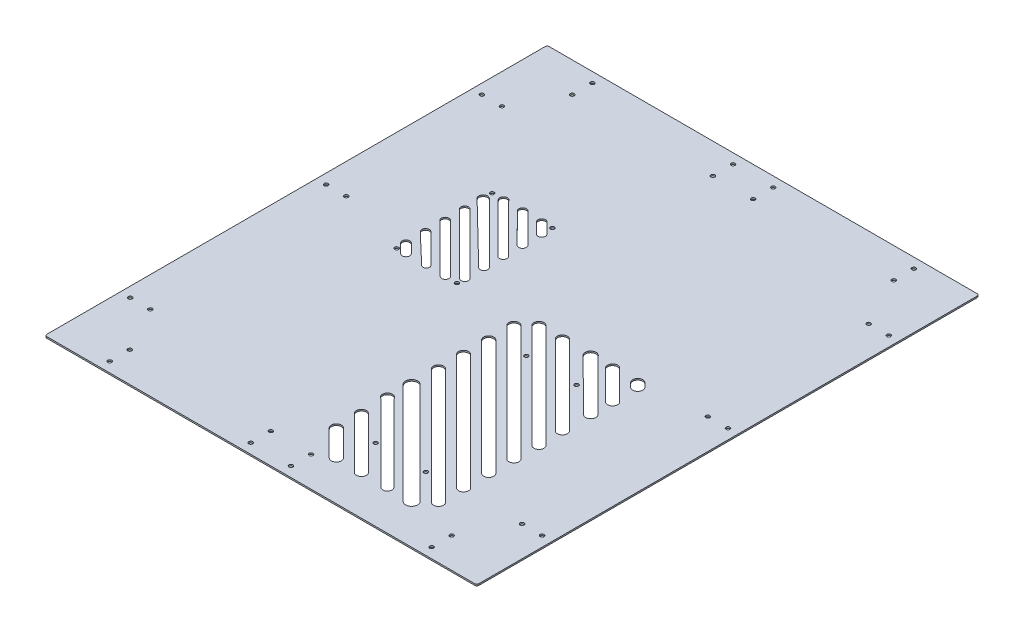
SolidWorks part; units mm, degrees
ref_plane "Front Plane" through (0, 0, 0) normal (0, 0, 1) x (1, 0, 0)
ref_plane "Top Plane" through (0, 0, 0) normal (0, 1, 0) x (1, 0, 0)
ref_plane "Right Plane" through (0, 0, 0) normal (1, 0, 0) x (0, 0, -1)
sketch "Sketch1" plane through (0, 0, 0) normal (0, 1, 0) x (1, 0, 0)
  line L1 (-215, -250) -> (215, -250)
  line L2 (-215, -250) -> (-215, 250)
  line L3 (-215, 250) -> (215, 250)
  line L4 (215, -250) -> (215, 250)
  line L5 (-215, -250) -> (215, 250) construction
  line L6 (-215, 250) -> (215, -250) construction
  point P0 (0, 0)
  dimension "D1" = 430
  dimension "D2" = 500
extrude "Boss-Extrude1" add sketch "Sketch1" along normal blind 1.5
sketch "Sketch6" plane through (0, 1.5, 0) normal (0, 1, 0) x (1, 0, 0)
  circle A0 centre (92.2927, -28) radius 1.95
  circle A1 centre (42.2927, -28) radius 1.95
  circle A2 centre (92.2927, -178) radius 1.95
  circle A3 centre (42.2927, -178) radius 1.95
  dimension "D1" = 50
  dimension "D2" = 150
sketch "Sketch7" plane through (0, 1.5, 0) normal (0, 1, 0) x (1, 0, 0)
  circle A0 centre (-114.98, 95.1924) radius 1.95
  circle A1 centre (-54.98, 95.1924) radius 1.95
  circle A2 centre (-54.98, 0.1924) radius 1.95
  circle A3 centre (-114.98, 0.1924) radius 1.95
  dimension "D1" = 95
  dimension "D2" = 60
sketch "Sketch12" plane through (0, 0, 0) normal (0, -1, 0) x (-1, 0, 0)
  line L0 (215, -250) -> (-215, -250) construction
  line L1 (-215, 250) -> (215, 250) construction
  line L2 (215, 250) -> (215, -250) construction
  line L3 (-215, -250) -> (-215, 250) construction
  circle A0 centre (-185, -175) radius 1.95
  circle A1 centre (-205, 170) radius 1.95
  circle A3 centre (-185, 10) radius 1.95
  circle A4 centre (-205, 10) radius 1.95
  circle A5 centre (-205, -175) radius 1.95
  circle A6 centre (-185, 170) radius 1.95
  circle A7 centre (205, -175) radius 1.95
  circle A8 centre (205, 20) radius 1.95
  circle A9 centre (185, 175) radius 1.95
  circle A10 centre (205, 175) radius 1.95
  circle A11 centre (185, -175) radius 1.95
  circle A12 centre (185, 20) radius 1.95
  circle A13 centre (160.3499, -240) radius 1.95
  circle A14 centre (160.3499, -220) radius 1.95
  circle A15 centre (20, -240) radius 1.95
  circle A16 centre (20, -220) radius 1.95
  circle A17 centre (-20, -220) radius 1.95
  circle A19 centre (-20, -240) radius 1.95
  circle A20 centre (-160, -240) radius 1.95
  circle A21 centre (-160, -220) radius 1.95
  circle A22 centre (160, 220) radius 1.95
  circle A23 centre (160, 240) radius 1.95
  circle A24 centre (20, 220) radius 1.95
  circle A25 centre (20, 240) radius 1.95
  circle A26 centre (-20, 220) radius 1.95
  circle A27 centre (-20, 240) radius 1.95
  circle A28 centre (-160, 220) radius 1.95
  circle A29 centre (-160, 240) radius 1.95
  dimension "D1" = 10
  dimension "D2" = 20
  dimension "D3" = 10
  dimension "D5" = 10
  dimension "D6" = 20
  dimension "D7" = 20
  dimension "D4" = 20
  dimension "D8" = 10
extrude "Cut-Extrude3" cut sketch "Sketch12" against normal blind 50.8
extrude "Cut-Extrude4" cut sketch "Sketch6" against normal blind 50.8
extrude "Cut-Extrude5" cut sketch "Sketch7" against normal blind 50.8
fillet "Fillet1" radius 2 4 edges at (215, 0.75, -250) (215, 0.75, 250) (-215, 0.75, 250) (-215, 0.75, -250)
sketch "Sketch13" plane through (0, 0, 0) normal (0, -1, 0) x (1, 0, 0)
  line L0 (67.2927, 28) -> (67.2927, 178) construction
  line L6 (92.2927, 178) -> (42.2927, 178) construction
  line L8 (92.2927, 178) -> (92.2927, 28) construction
  line L9 (92.2927, 28) -> (42.2927, 28) construction
  line L10 (42.2927, 178) -> (42.2927, 28) construction
  line L11 (67.2927, 103) -> (42.2927, 103) construction
  line L12 (124.7927, 122.9451) -> (9.7927, 7.9451) construction
  line L13 (124.7927, 210.5) -> (9.7927, 210.5)
  line L14 (124.7927, 210.5) -> (124.7927, -4.5)
  line L15 (124.7927, -4.5) -> (9.7927, -4.5)
  line L16 (9.7927, 210.5) -> (9.7927, -4.5)
  line L17 (124.7927, 210.5) -> (9.7927, -4.5) construction
  line L18 (124.7927, -4.5) -> (9.7927, 210.5) construction
  line L19 (128.3282, 119.4095) -> (13.3282, 4.4095)
  line L20 (121.2572, 126.4806) -> (6.2572, 11.4806)
  line L21 (124.7927, 147.9451) -> (9.7927, 32.9451) construction
  line L22 (128.3282, 144.4095) -> (13.3282, 29.4095)
  line L23 (121.2572, 151.4806) -> (6.2572, 36.4806)
  line L26 (124.7927, 172.9451) -> (9.7927, 57.9451) construction
  line L29 (128.3282, 169.4095) -> (13.3282, 54.4095)
  line L32 (121.2572, 176.4806) -> (6.2572, 61.4806)
  line L35 (124.7927, 197.9451) -> (9.7927, 82.9451) construction
  line L38 (128.3282, 194.4095) -> (13.3282, 79.4095)
  line L41 (121.2572, 201.4806) -> (6.2572, 86.4806)
  line L44 (110.6506, 210.5) -> (9.7927, 109.6421) construction
  line L47 (114.8916, 206.259) -> (14.0337, 105.4011)
  line L50 (102.1686, 210.5) -> (5.5517, 113.8831)
  line L53 (-54.98, -95.1924) -> (-114.98, -95.1924) construction
  line L58 (-114.98, -95.1924) -> (-114.98, -44.2867) construction
  line L62 (86.5307, 210.5) -> (8.6916, 132.661) construction
  line L65 (-114.98, -0.1924) -> (-54.98, -0.1924) construction
  line L66 (-54.98, -0.1924) -> (-54.98, -95.1924) construction
  line L67 (-54.98, -84.5868) -> (-65.5855, -95.1924) construction
  line L68 (-54.98, -89.8901) -> (-60.2822, -95.1924)
  line L69 (-57.6303, -81.9365) -> (-68.2358, -92.5421)
  line L70 (-54.98, -95.1924) -> (-114.98, -0.1924) construction
  line L71 (-54.98, -65.4331) -> (-84.7393, -95.1924) construction
  line L72 (-54.98, -70.7364) -> (-79.4324, -95.1924)
  line L73 (-57.6384, -62.7886) -> (-87.2428, -92.5491)
  line L74 (-54.98, -46.2793) -> (-103.893, -95.1924) construction
  line L75 (-54.98, -51.5826) -> (-98.5897, -95.1924)
  line L76 (-57.6398, -43.6363) -> (-106.2442, -92.5505)
  line L77 (-54.98, -27.1256) -> (-120.2706, -91.5396) construction
  line L78 (-54.98, -32.4289) -> (-111.9255, -89.3745)
  line L79 (-57.5955, -24.4383) -> (-117.9928, -83.2246)
  line L80 (-52.4189, -5.4139) -> (-114.98, -67.9718) construction
  line L81 (-52.3742, -10.6694) -> (-112.3283, -70.6235)
  line L83 (-63.9533, 2.3637) -> (-114.98, -48.8181) construction
  line L84 (-63.9494, -2.7446) -> (-112.3283, -51.1235)
  line L87 (-71.6576, -0.1924) -> (-114.98, -43.5148)
  line L88 (-85.508, -0.1924) -> (-114.98, -29.6644) construction
  line L91 (-83.2026, -2.4978) -> (-112.3283, -31.6235)
  line L92 (-90.2324, -0.1924) -> (-114.98, -23.7903)
  line L93 (-105.7005, -0.1924) -> (-114.98, -10.5106) construction
  line L96 (-103.0489, -2.844) -> (-112.3283, -12.1235)
  line L99 (-111.0038, -0.1924) -> (-114.98, -4.1685)
  line L102 (-60.2822, -95.1924) -> (-62.9366, -97.844)
  line L105 (-98.5897, -95.1924) -> (-100.7736, -97.6705)
  line L106 (-79.4324, -95.1924) -> (-81.8594, -97.7646)
  line L107 (-114.98, -62.6685) -> (-117.6316, -65.3202)
  line L108 (-114.98, -43.5148) -> (-117.4324, -45.635)
  line L109 (-114.98, -4.1685) -> (-117.6316, -6.8202)
  line L110 (-54.98, -89.8901) -> (-52.3283, -87.2358)
  line L111 (-54.98, -70.7364) -> (-52.3283, -68.0843)
  line L112 (-54.98, -51.5826) -> (-52.3283, -48.9306)
  line L113 (-54.98, -32.4289) -> (-52.3283, -29.7772)
  line L114 (-57.5857, -5.4578) -> (-114.98, -62.6685)
  line L115 (-90.2324, -0.1924) -> (-87.7579, 2.1672)
  line L116 (-71.6576, -0.1924) -> (-69.0283, 2.3851)
  line L117 (-111.0038, -0.1924) -> (-108.3522, 2.4593)
  line L118 (-114.98, -23.7903) -> (-117.5678, -26.2579)
  line L119 (89.7127, 207.318) -> (13.4147, 131.0201)
  line L120 (80.1667, 210.5) -> (7.0508, 137.3841)
  line L121 (60.6506, 210.5) -> (9.7927, 159.6421) construction
  line L122 (64.1861, 206.9645) -> (13.3282, 156.1066)
  line L123 (53.5795, 210.5) -> (6.2572, 163.1777)
  line L124 (35.6506, 210.5) -> (9.7927, 184.6421) construction
  line L125 (39.1861, 206.9645) -> (13.3282, 181.1066)
  line L126 (28.5795, 210.5) -> (6.2572, 188.1777)
  line L127 (10.6506, 210.5) -> (9.7927, 209.6421) construction
  line L128 (16.6674, 209.4458) -> (13.3282, 206.1066)
  line L130 (128.3284, -3.8936) -> (124.1859, -8.0357)
  line L133 (125.6429, 98.792) -> (22.3509, -4.5) construction
  line L134 (129.1784, 95.2564) -> (29.422, -4.5)
  line L135 (122.1073, 102.3275) -> (18.8154, -0.9645)
  line L136 (124.7927, 74.6421) -> (45.6506, -4.5) construction
  line L137 (128.3282, 71.1066) -> (52.7216, -4.5)
  line L138 (121.2572, 78.1777) -> (42.115, -0.9645)
  line L139 (124.7927, 46.436) -> (73.8567, -4.5) construction
  line L140 (128.4341, 42.7783) -> (80.9436, -4.5)
  line L141 (121.1513, 50.0937) -> (70.1015, -0.728)
  line L142 (124.7927, 24.6421) -> (95.6506, -4.5) construction
  line L143 (128.3282, 21.1066) -> (102.7216, -4.5)
  line L144 (121.2572, 28.1777) -> (92.115, -0.9645)
  line L145 (124.7928, -0.358) -> (120.6506, -4.5) construction
  line L147 (121.2572, 3.1777) -> (117.115, -0.9645)
  line L166 (6.6802, 213.5553) -> (10.376, 216.4949)
  line L167 (28.5795, 210.5) -> (32.115, 214.0355)
  line L168 (53.5795, 210.5) -> (57.115, 214.0355)
  line L169 (80.1667, 210.5) -> (83.3487, 213.682)
  line L170 (102.1686, 210.5) -> (106.4096, 214.741)
  line L171 (102.7216, -4.5) -> (99.1861, -8.0355)
  line L172 (80.9436, -4.5) -> (77.854, -8.0143)
  line L173 (52.7216, -4.5) -> (49.1861, -8.0355)
  line L174 (29.422, -4.5) -> (25.8864, -8.0355)
  line L356 (124.7927, 347.9451) -> (9.7927, 232.9451) construction
  line L357 (128.3282, 344.4095) -> (13.3282, 229.4095) [skipped]
  line L358 (121.2572, 351.4806) -> (6.2572, 236.4806) [skipped]
  line L359 (124.7927, 322.9451) -> (9.7927, 207.9451) construction
  line L360 (128.3282, 319.4095) -> (13.3282, 204.4095) [skipped]
  line L361 (121.2572, 326.4806) -> (6.2572, 211.4806) [skipped]
  line L362 (124.7927, 297.9451) -> (9.7927, 182.9451) construction
  line L363 (128.3282, 294.4095) -> (13.3282, 179.4095) [skipped]
  line L364 (121.2572, 301.4806) -> (6.2572, 186.4806) [skipped]
  line L365 (124.7927, 272.9451) -> (9.7927, 157.9451) construction
  line L366 (128.3282, 269.4095) -> (13.3282, 154.4095) [skipped]
  line L367 (121.2572, 276.4806) -> (6.2572, 161.4806) [skipped]
  line L368 (124.7927, 247.9451) -> (9.7927, 132.9451) construction
  line L369 (128.3282, 244.4095) -> (13.3282, 129.4095) [skipped]
  line L370 (121.2572, 251.4806) -> (6.2572, 136.4806) [skipped]
  line L371 (124.7927, 222.9451) -> (9.7927, 107.9451) construction
  line L372 (128.3282, 219.4095) -> (13.3282, 104.4095) [skipped]
  line L373 (121.2572, 226.4806) -> (6.2572, 111.4806) [skipped]
  line L374 (124.7927, 347.9451) -> (9.7927, 232.9451) construction
  line L375 (128.3282, 344.4095) -> (13.3282, 229.4095) [skipped]
  line L376 (121.2572, 351.4806) -> (6.2572, 236.4806) [skipped]
  line L377 (124.7927, 322.9451) -> (9.7927, 207.9451) construction
  line L378 (128.3282, 319.4095) -> (13.3282, 204.4095) [skipped]
  line L379 (121.2572, 326.4806) -> (6.2572, 211.4806) [skipped]
  line L380 (124.7927, 297.9451) -> (9.7927, 182.9451) construction
  line L381 (128.3282, 294.4095) -> (13.3282, 179.4095) [skipped]
  line L382 (121.2572, 301.4806) -> (6.2572, 186.4806) [skipped]
  line L383 (124.7927, 272.9451) -> (9.7927, 157.9451) construction
  line L384 (128.3282, 269.4095) -> (13.3282, 154.4095) [skipped]
  line L385 (121.2572, 276.4806) -> (6.2572, 161.4806) [skipped]
  line L386 (124.7927, 247.9451) -> (9.7927, 132.9451) construction
  line L387 (128.3282, 244.4095) -> (13.3282, 129.4095) [skipped]
  line L388 (121.2572, 251.4806) -> (6.2572, 136.4806) [skipped]
  line L389 (124.7927, 222.9451) -> (9.7927, 107.9451) construction
  line L390 (128.3282, 219.4095) -> (13.3282, 104.4095) [skipped]
  line L391 (121.2572, 226.4806) -> (6.2572, 111.4806) [skipped]
  arc A32 (128.3282, 119.4095) -> (121.2572, 126.4806) centre (124.7927, 122.9451) ccw
  arc A59 (-68.2358, -92.5421) -> (-62.9366, -97.844) centre (-65.5855, -95.1924) ccw
  arc A60 (-87.2428, -92.5491) -> (-81.8594, -97.7646) centre (-84.5855, -95.1924) ccw
  arc A61 (-106.2442, -92.5505) -> (-100.7736, -97.6705) centre (-103.5855, -95.1924) ccw
  arc A63 (-117.6316, -65.3202) -> (-112.3283, -70.6235) centre (-114.98, -67.9718) ccw
  arc A64 (-117.4324, -45.635) -> (-112.3283, -51.1235) centre (-114.98, -48.4718) ccw
  arc A65 (-117.5678, -26.2579) -> (-112.3283, -31.6235) centre (-114.98, -28.9718) ccw
  arc A66 (-117.6316, -6.8202) -> (-112.3283, -12.1235) centre (-114.98, -9.4718) ccw
  arc A67 (-52.3283, -29.7772) -> (-57.5955, -24.4383) centre (-54.98, -27.1256) ccw
  arc A68 (-52.3283, -48.9306) -> (-57.6398, -43.6363) centre (-54.98, -46.2793) ccw
  arc A69 (-52.3283, -68.0843) -> (-57.6384, -62.7886) centre (-54.98, -65.4331) ccw
  arc A70 (-52.3283, -87.2358) -> (-57.6303, -81.9365) centre (-54.98, -84.5868) ccw
  arc A71 (-52.3742, -10.6694) -> (-57.5857, -5.4578) centre (-54.98, -8.0636) ccw
  arc A72 (-117.9928, -83.2246) -> (-111.9255, -89.3745) centre (-114.98, -86.32) ccw
  arc A73 (6.2572, 11.4806) -> (13.3282, 4.4095) centre (9.7927, 7.9451) ccw
  arc A74 (128.3282, 144.4095) -> (121.2572, 151.4806) centre (124.7927, 147.9451) ccw
  arc A75 (6.2572, 36.4806) -> (13.3282, 29.4095) centre (9.7927, 32.9451) ccw
  arc A76 (128.3282, 169.4095) -> (121.2572, 176.4806) centre (124.7927, 172.9451) ccw
  arc A77 (6.2572, 61.4806) -> (13.3282, 54.4095) centre (9.7927, 57.9451) ccw
  circle A78 centre (-122.5855, -95.1924) radius 3.7481 [skipped]
  arc A79 (-83.2026, -2.4978) -> (-87.7579, 2.1672) centre (-85.508, -0.1924) ccw
  arc A80 (-103.0489, -2.844) -> (-108.3522, 2.4593) centre (-105.7005, -0.1924) ccw
  arc A81 (-63.9494, -2.7446) -> (-69.0283, 2.3851) centre (-66.5016, -0.1924) ccw
  arc A82 (128.3282, 194.4095) -> (121.2572, 201.4806) centre (124.7927, 197.9451) ccw
  arc A83 (6.2572, 86.4806) -> (13.3282, 79.4095) centre (9.7927, 82.9451) ccw
  arc A85 (5.5517, 113.8831) -> (14.0337, 105.4011) centre (9.7927, 109.6421) ccw
  arc A87 (7.0508, 137.3841) -> (13.4147, 131.0201) centre (8.6916, 132.661) ccw
  arc A89 (6.2572, 163.1777) -> (13.3282, 156.1066) centre (9.7927, 159.6421) ccw
  arc A91 (6.2572, 188.1777) -> (13.3282, 181.1066) centre (9.7927, 184.6421) ccw
  arc A93 (6.6802, 213.5553) -> (13.3282, 206.1066) centre (9.7927, 209.6421) ccw
  arc A96 (129.1784, 95.2564) -> (122.1073, 102.3275) centre (125.6429, 98.792) ccw
  arc A98 (128.3282, 71.1066) -> (121.2572, 78.1777) centre (124.7927, 74.6421) ccw
  arc A100 (128.4341, 42.7783) -> (121.1513, 50.0937) centre (124.7927, 46.436) ccw
  arc A102 (128.3282, 21.1066) -> (121.2572, 28.1777) centre (124.7927, 24.6421) ccw
  arc A104 (128.3284, -3.8936) -> (121.2572, 3.1777) centre (124.7928, -0.358) ccw
  arc A118 (117.115, -0.9645) -> (124.1859, -8.0357) centre (120.6506, -4.5) ccw
  arc A119 (92.115, -0.9645) -> (99.1861, -8.0355) centre (95.6506, -4.5) ccw
  arc A120 (70.1015, -0.728) -> (77.854, -8.0143) centre (73.8567, -4.5) ccw
  arc A121 (42.115, -0.9645) -> (49.1861, -8.0355) centre (45.6506, -4.5) ccw
  arc A122 (18.8154, -0.9645) -> (25.8864, -8.0355) centre (22.3509, -4.5) ccw
  arc A123 (114.8916, 206.259) -> (106.4096, 214.741) centre (110.6506, 210.5) ccw
  arc A124 (89.7127, 207.318) -> (83.3487, 213.682) centre (86.5307, 210.5) ccw
  arc A125 (64.1861, 206.9645) -> (57.115, 214.0355) centre (60.6506, 210.5) ccw
  arc A126 (39.1861, 206.9645) -> (32.115, 214.0355) centre (35.6506, 210.5) ccw
  arc A127 (16.6674, 209.4458) -> (10.376, 216.4949) centre (13.3216, 212.7917) ccw
  arc A261 (128.3282, 344.4095) -> (121.2572, 351.4806) centre (124.7927, 347.9451) ccw [skipped]
  arc A262 (6.2572, 236.4806) -> (13.3282, 229.4095) centre (9.7927, 232.9451) ccw [skipped]
  arc A263 (128.3282, 319.4095) -> (121.2572, 326.4806) centre (124.7927, 322.9451) ccw [skipped]
  arc A264 (6.2572, 211.4806) -> (13.3282, 204.4095) centre (9.7927, 207.9451) ccw [skipped]
  arc A265 (128.3282, 294.4095) -> (121.2572, 301.4806) centre (124.7927, 297.9451) ccw [skipped]
  arc A266 (6.2572, 186.4806) -> (13.3282, 179.4095) centre (9.7927, 182.9451) ccw [skipped]
  arc A267 (128.3282, 269.4095) -> (121.2572, 276.4806) centre (124.7927, 272.9451) ccw [skipped]
  arc A268 (6.2572, 161.4806) -> (13.3282, 154.4095) centre (9.7927, 157.9451) ccw [skipped]
  arc A269 (128.3282, 244.4095) -> (121.2572, 251.4806) centre (124.7927, 247.9451) ccw [skipped]
  arc A270 (6.2572, 136.4806) -> (13.3282, 129.4095) centre (9.7927, 132.9451) ccw [skipped]
  arc A271 (128.3282, 219.4095) -> (121.2572, 226.4806) centre (124.7927, 222.9451) ccw [skipped]
  arc A272 (6.2572, 111.4806) -> (13.3282, 104.4095) centre (9.7927, 107.9451) ccw [skipped]
  point P18 (67.2927, 65.4451)
  point P23 (67.2927, 90.4451)
  point P30 (67.2927, 115.4451)
  point P37 (67.2927, 140.4451)
  point P46 (67.2927, 167.1421)
  point P54 (67.2927, 192.1421)
  point P73 (67.2927, 217.1421)
  point P85 (67.2927, 153)
  point P89 (-59.0853, -88.6922)
  point P94 (67.2927, 42.1421)
  point P102 (67.2927, 17.1421)
  point P116 (67.2927, 193)
  point P124 (-66.4512, -76.9043)
  point P125 (67.2927, 173)
  point P135 (-73.8171, -65.1165)
  point P151 (-81.183, -53.3286)
  point P153 (67.2927, 193)
  point P156 (67.2927, 292.1421)
  point P159 (-88.5489, -41.5407)
  point P160 (67.2927, 173)
  point P167 (67.2927, 153)
  point P168 (-95.9147, -29.7529)
  point P174 (67.2927, 193)
  point P176 (-103.2806, -17.965)
  point P181 (67.2927, 173)
  point P184 (-110.6465, -6.1771)
  point P188 (67.2927, 153)
  point P207 (67.2927, 267.1421)
  point P227 (67.2927, 242.1421)
  point P235 (67.2927, 192.1421)
  point P242 (67.2927, 167.1421)
  point P251 (67.2927, 193)
  point P258 (67.2927, 173)
  point P265 (67.2927, 153)
  point P272 (67.2927, 193)
  point P279 (67.2927, 173)
  point P286 (67.2927, 153)
  point P321 (67.2927, 193)
  point P328 (67.2927, 173)
  point P335 (67.2927, 153)
  point P342 (67.2927, 193)
  point P349 (67.2927, 173)
  point P356 (67.2927, 153)
  point P365 (67.2927, 193)
  point P372 (67.2927, 173)
  point P379 (67.2927, 153)
  point P386 (67.2927, 193)
  point P393 (67.2927, 173)
  point P400 (67.2927, 153)
  point P407 (67.2927, 193)
  point P414 (67.2927, 173)
  point P421 (67.2927, 153)
  point P428 (67.2927, 193)
  point P435 (67.2927, 173)
  point P442 (67.2927, 153)
  point P449 (67.2927, 193)
  point P456 (67.2927, 173)
  point P463 (67.2927, 153)
  point P470 (67.2927, 193)
  point P477 (67.2927, 173)
  point P484 (67.2927, 153)
  point P491 (67.2927, 193)
  point P498 (67.2927, 173)
  point P505 (67.2927, 153)
  point P512 (67.2927, 193)
  point P519 (67.2927, 173)
  point P526 (67.2927, 153)
  point P533 (67.2927, 193)
  point P540 (67.2927, 173)
  point P547 (67.2927, 153)
  point P554 (67.2927, 193)
  point P561 (67.2927, 173)
  point P568 (67.2927, 153)
  point P575 (67.2927, 193)
  point P582 (67.2927, 173)
  point P589 (67.2927, 153)
  point P596 (67.2927, 193)
  point P603 (67.2927, 173)
  point P610 (67.2927, 153)
  point P617 (67.2927, 193)
  point P624 (67.2927, 173)
  point P631 (67.2927, 153)
  point P638 (67.2927, 193)
  point P645 (67.2927, 173)
  point P652 (67.2927, 153)
  point P677 (67.2927, 292.1421)
  point P684 (67.2927, 267.1421)
  point P691 (67.2927, 242.1421)
  point P698 (67.2927, 217.1421)
  point P705 (67.2927, 192.1421)
  point P712 (67.2927, 167.1421)
  point P719 (67.2927, 288.6066)
  point P726 (67.2927, 263.6066)
  point P733 (67.2927, 238.6066)
  point P740 (67.2927, 213.6066)
  point P747 (67.2927, 188.6066)
  point P754 (67.2927, 163.6066)
  point P761 (67.2927, 288.6066)
  point P768 (67.2927, 263.6066)
  point P775 (67.2927, 238.6066)
  point P782 (67.2927, 213.6066)
  point P789 (67.2927, 188.6066)
  point P796 (67.2927, 163.6066)
  point P803 (67.2927, 288.6066)
  point P810 (67.2927, 263.6066)
  point P817 (67.2927, 238.6066)
  point P824 (67.2927, 213.6066)
  point P831 (67.2927, 188.6066)
  point P838 (67.2927, 163.6066)
  point P845 (67.2927, 288.6066)
  point P852 (67.2927, 263.6066)
  point P859 (67.2927, 238.6066)
  point P866 (67.2927, 213.6066)
  point P873 (67.2927, 188.6066)
  point P880 (67.2927, 163.6066)
  point P887 (67.2927, 288.6066)
  point P894 (67.2927, 263.6066)
  point P901 (67.2927, 238.6066)
  point P908 (67.2927, 213.6066)
  point P915 (67.2927, 188.6066)
  point P922 (67.2927, 163.6066)
  point P929 (67.2927, 288.6066)
  point P936 (67.2927, 263.6066)
  point P943 (67.2927, 238.6066)
  point P950 (67.2927, 213.6066)
  point P957 (67.2927, 188.6066)
  point P964 (67.2927, 163.6066)
  point P971 (67.2927, 289.3137)
  point P978 (67.2927, 264.3137)
  point P985 (67.2927, 239.3137)
  point P992 (67.2927, 214.3137)
  point P999 (67.2927, 189.3137)
  point P1006 (67.2927, 164.3137)
  point P1013 (67.2927, 289.3137)
  point P1020 (67.2927, 264.3137)
  point P1027 (67.2927, 239.3137)
  point P1034 (67.2927, 214.3137)
  point P1041 (67.2927, 189.3137)
  point P1048 (67.2927, 164.3137)
  point P1055 (67.2927, 290.4451)
  point P1062 (67.2927, 265.4451)
  point P1069 (67.2927, 240.4451)
  point P1076 (67.2927, 215.4451)
  point P1083 (67.2927, 190.4451)
  point P1090 (67.2927, 165.4451)
  point P1097 (67.2927, 290.4451)
  point P1104 (67.2927, 265.4451)
  point P1111 (67.2927, 240.4451)
  point P1118 (67.2927, 215.4451)
  point P1125 (67.2927, 190.4451)
  point P1132 (67.2927, 165.4451)
  point P1139 (67.2927, 290.4451)
  point P1146 (67.2927, 265.4451)
  point P1153 (67.2927, 240.4451)
  point P1160 (67.2927, 215.4451)
  point P1167 (67.2927, 190.4451)
  point P1174 (67.2927, 165.4451)
  dimension "D1" = 115
  dimension "D5" = 45
  dimension "D6" = 4
  dimension "D7" = 4
  dimension "D8" = 45
  dimension "D9" = 3.8
  dimension "D10" = 10
  dimension "D2" = 215
  dimension "D3" = 45
  dimension "D4" = 5
  dimension "D11" = 7.68
  dimension "D12" = 10
  dimension "D13" = 9
  dimension "D14" = 45
  dimension "D15" = 45
  dimension "D16" = 5
  dimension "D17" = 3.8
extrude "Cut-Extrude6" cut sketch "Sketch13" against normal blind 10 contours L69 A59 L102 L68 L110 A70 | A69 L73 A60 L106 L72 L111 | L75 L105 A61 L76 A68 L112 | A67 L79 A72 L78 L113 | L81 A63 L107 L114 A71 | L108 A64 L84 A81 L116 L87 | A65 L91 A79 L115 L92 L118 | L96 A66 L109 L99 L117 A80 | A125 L168 L123 A89 L122 | A126 L167 L126 A91 L125 | L119 A87 L120 L169 A124 | A123 L170 L50 A85 L47 | L38 A83 L41 A82 | L29 A77 L32 A76 | L22 A75 L23 A74 | L20 A73 L19 A32 | L135 A122 L174 L134 A96 | L138 A121 L173 L137 A98 | L141 A120 L172 L140 A100 | L144 A119 L171 L143 A102 | L147 A118 L130 A104
